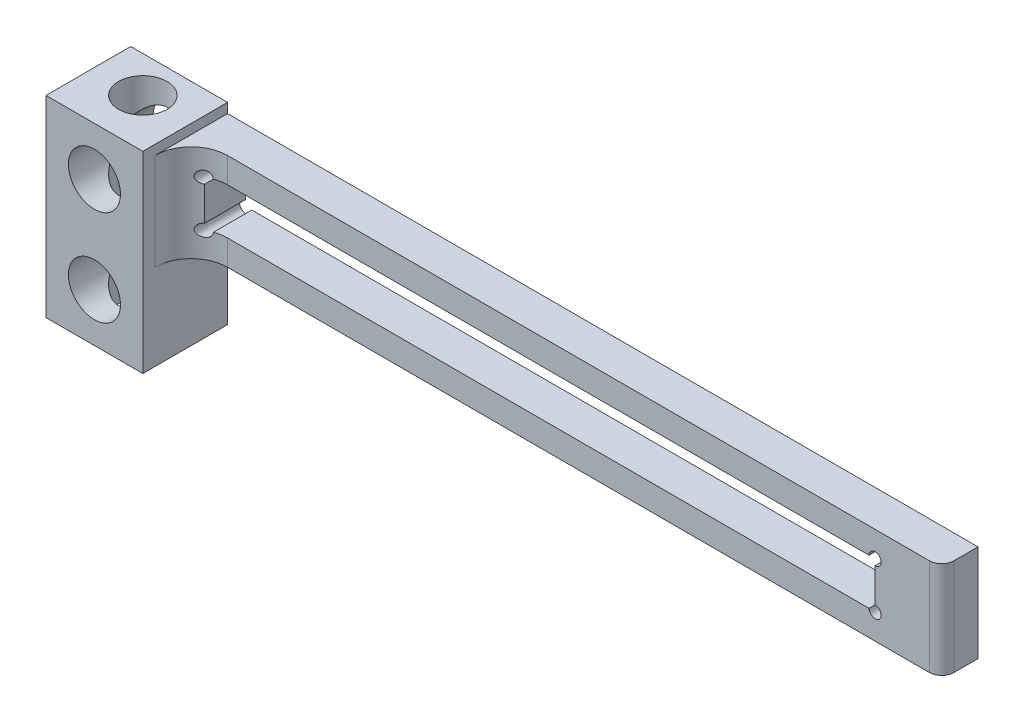
SolidWorks part; units mm, degrees
material "ABS"
ref_plane "Ebene vorne" through (0, 0, 0) normal (0, 0, 1) x (1, 0, 0)
ref_plane "Ebene oben" through (0, 0, 0) normal (0, 1, 0) x (1, 0, 0)
ref_plane "Ebene rechts" through (0, 0, 0) normal (1, 0, 0) x (0, 0, -1)
sketch "Skizze1" plane through (0, 0, 0) normal (0, 0, 1) x (1, 0, 0)
  line L0 (-35, 0) -> (35, 0) construction
  line L1 (-35, 4) -> (35, 4)
  line L2 (-35, 4) -> (-35, -4)
  line L3 (-35, -4) -> (35, -4)
  line L4 (35, 4) -> (35, -4)
  line L5 (-35, 4) -> (35, -4) construction
  line L6 (-35, -4) -> (35, 4) construction
  line L8 (-25.5, 1.9) -> (29.5, 1.9)
  line L9 (-25.5, 1.9) -> (-25.5, -1.9)
  line L10 (-25.5, -1.9) -> (29.5, -1.9)
  line L11 (29.5, 1.9) -> (29.5, -1.9)
  point P0 (0, 0)
  dimension "D1" = 70
  dimension "D2" = 8
  dimension "D3" = 1.9
  dimension "D4" = 1.9
  dimension "D5" = 3.8
  dimension "D6" = 9.5
  dimension "D7" = 55
extrude "Body" add sketch "Skizze1" along normal mid plane 3
sketch "Lochungsskizze" plane through (0, 0, 1.5) normal (0, 0, 1) x (1, 0, 0)
  circle A0 centre (-25.5, 1.9) radius 0.5
  circle A1 centre (-25.5, -1.9) radius 0.5
  circle A2 centre (29.5, -1.9) radius 0.5
  circle A3 centre (29.5, 1.9) radius 0.5
  dimension "D1" = 1
extrude "RahmenLochungen" cut sketch "Lochungsskizze" against normal through all
fillet "Verrundung1" radius 1 1 edges at (35, 0, 1.5)
sketch "Skizze2" plane through (0, 0, 1.5) normal (0, 0, 1) x (1, 0, 0)
  line L0 (-35, 0) -> (-25.5, 0) construction
  line L1 (-35, 4) -> (-35, -4) construction
  line L2 (-25.5, 1.4) -> (-25.5, -1.4) construction
  line L3 (-35, 0) -> (-35, -11.1)
  line L4 (-35, -11.1) -> (-27, -11.1)
  line L5 (-27, -11.1) -> (-27, 0)
  line L6 (-35, 0) -> (-35, 4.8)
  line L7 (-35, 4.8) -> (-27, 4.8)
  line L8 (-27, 4.8) -> (-27, 0)
  dimension "D1" = 8
  dimension "D2" = 11.1
  dimension "D3" = 4.8
extrude "Schnabel" add sketch "Skizze2" along normal mid plane 6
sketch "Schnabelaufsatzskizze" plane through (0, 0, 4.5) normal (0, 0, 1) x (1, 0, 0)
  line L1 (-35, 4.8) -> (-27, 4.8)
  line L2 (-35, 4.8) -> (-35, -11.1)
  line L3 (-35, -11.1) -> (-27, -11.1)
  line L4 (-27, 4.8) -> (-27, -11.1)
extrude "Schnabelaufsatz" add sketch "Schnabelaufsatzskizze" along normal blind 1
sketch "Skizze4" plane through (0, 4.8, 0) normal (0, 1, 0) x (1, 0, 0)
  line L0 (-35, -5.5) -> (-35, 1.5) construction
  line L1 (-27, 1.5) -> (-35, 1.5) construction
  circle A0 centre (-31, -1.5) radius 2
  dimension "D1" = 4
  dimension "D3" = 4
  dimension "D2" = 3
extrude "lochungHorizontal" cut sketch "Skizze4" against normal through all both and the other way through all contours A0
sketch "Skizze5" plane through (0, 0, 5.5) normal (0, 0, 1) x (1, 0, 0)
  line L0 (-31, 4.8) -> (-31, -11.1) construction
  line L1 (-27, 4.8) -> (-35, 4.8) construction
  line L2 (-35, -11.1) -> (-27, -11.1) construction
  circle A0 centre (-31, 0.8) radius 2.15
  circle A1 centre (-31, -7.1) radius 2.15
  dimension "D1" = 4.3
  dimension "D2" = 4
  dimension "D3" = 4
extrude "lochung2" cut sketch "Skizze5" against normal through all
fillet "Verrundung4" radius 3 1 edges at (-27, 0, 1.5)
